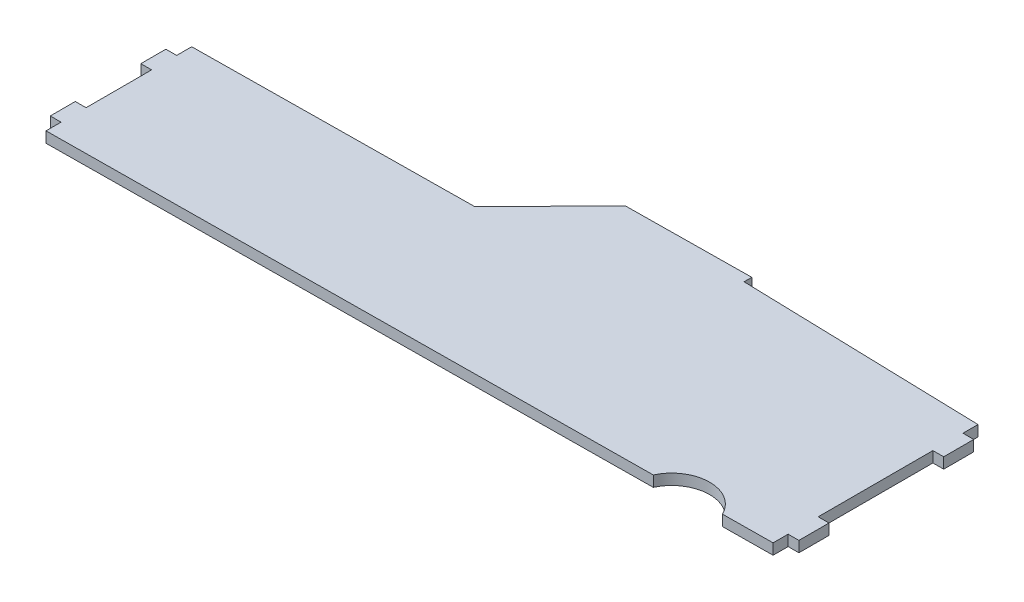
SolidWorks part; units mm, degrees
note: '?' marks a value the reader was unsure of.
material "Acrylic (Medium-high impact)"
ref_plane "Front" through (0, 0, 0) normal (0, 0, 1) x (1, 0, 0)
ref_plane "Top" through (0, 0, 0) normal (0, 1, 0) x (1, 0, 0)
ref_plane "Right" through (0, 0, 0) normal (1, 0, 0) x (0, 0, -1)
ref_axis "side-side" through (80.9, 0, 0) along (-1, 0, 0)?
ref_axis "up-down" through (0, 50, 0) along (0, -1, 0)?
ref_axis "front-back" through (0, 0, -80.9) along (0, 0, 1)?
sketch3d "3DSketch1"
  line L1 (106.3085, 18.7792, 112.386) -> (-144.3396, -7.2886, 112.0046)
  line L2 (106.3085, 18.7792, 112.386) -> (111.2529, -28.6891, 107.3699)
  line L10 (149.9635, -49.7721, 83.9204) -> (150.2559, -52.5791, 110.7725)
  line L11 (146.8969, -20.3316, 84.5177) -> (149.6788, -47.0392, 81.6954)
  line L12 (146.9185, -20.5396, 86.5067) -> (146.8969, -20.3316, 84.5177)
  line L13 (149.752, -47.7417, 83.6322) -> (146.9185, -20.5396, 86.5067)
  line L14 (150.0552, -50.6528, 111.4788) -> (149.752, -47.7417, 83.6322)
  line L15 (147.2218, -23.4506, 114.3533) -> (150.0552, -50.6528, 111.4788)
  line L16 (147.2434, -23.6585, 116.3424) -> (147.2218, -23.4506, 114.3533)
  line L17 (150.0254, -50.3661, 113.5201) -> (147.2434, -23.6585, 116.3424)
  line L18 (149.9635, -49.7721, 83.9204) -> (150.2559, -52.5791, 110.7725)
  line L19 (146.8969, -20.3316, 84.5177) -> (149.6788, -47.0392, 81.6954)
  line L20 (146.9185, -20.5396, 86.5067) -> (146.8969, -20.3316, 84.5177)
  line L21 (149.752, -47.7417, 83.6322) -> (146.9185, -20.5396, 86.5067)
  line L22 (150.0552, -50.6528, 111.4788) -> (149.752, -47.7417, 83.6322)
  line L23 (147.2218, -23.4506, 114.3533) -> (150.0552, -50.6528, 111.4788)
  line L24 (147.2434, -23.6585, 116.3424) -> (147.2218, -23.4506, 114.3533)
  line L25 (150.0254, -50.3661, 113.5201) -> (147.2434, -23.6585, 116.3424)
  arc A2 (149.6788, -47.0392, 81.6954) -> (149.9635, -49.7721, 83.9204) centre (149.7059, -47.2991, 84.1817) ccw
  arc A3 (150.2559, -52.5791, 110.7725) -> (150.0254, -50.3661, 113.5201) centre (149.9983, -50.1062, 111.0338) ccw
  arc A4 (149.6788, -47.0392, 81.6954) -> (149.9635, -49.7721, 83.9204) centre (149.7059, -47.2991, 84.1817) ccw
  arc A5 (150.2559, -52.5791, 110.7725) -> (150.0254, -50.3661, 113.5201) centre (149.9983, -50.1062, 111.0338) ccw
  point P16 (147.2193, -47.5581, 84.1817)
  point P19 (147.5117, -50.3652, 111.0338)
  point P20 (147.2193, -47.5581, 84.1817)
  point P21 (147.5117, -50.3652, 111.0338)
  dimension "D1" = 0
ref_plane "Plane1" through (1.0322, -11.5374, 110.1981) normal (-0.0093, 0.1041, -0.9945) x (-1, -0.001, 0.0093)
sketch "Sketch3" plane through (1.0322, -11.5374, 110.1981) normal (-0.0093, 0.1041, -0.9945) x (-1, -0.001, 0.0093)
  line L0 (-98.6079, 94.7953) -> (-113.8605, -52.442)
  line L1 (-98.6079, 94.7953) -> (205.7196, 63.2694)
  line L2 (-113.8605, -52.442) -> (190.4669, -83.9679)
  line L3 (205.7196, 63.2694) -> (190.4669, -83.9679)
  line L4 (-105.2808, 30.3799) -> (-110.2255, -17.3527) construction
surface "Surface-Plane1" sketch "Sketch3"
sketch "Sketch4" plane through (0, 0, 0) normal (0, 1, 0) x (1, 0, 0)
  line L0 (-199.3464, -113.2829) -> (108.2646, -110.4016)
  line L1 (-126.8098, -112.6035) -> (117.9865, -110.3105) construction
  line L2 (-144.7791, -48.6057) -> (-144.7791, 135.3125)
  line L3 (-144.7791, -48.6057) -> (-144.7791, 135.3125) construction
  line L4 (144.7791, -22.2698) -> (144.7791, 138.5677)
  line L5 (144.7791, -22.2698) -> (144.7791, 164.8582) construction
  line L6 (47.7369, -6.0182) -> (47.7369, 41.5356)
  line L7 (47.7369, -13.6104) -> (47.7369, -10.5185)
  line L8 (47.7369, -6.0182) -> (42.6294, -6.0738)
  line L9 (5.3488, -6.4798) -> (-6.8682, -6.6128)
  line L10 (5.3488, -6.4798) -> (-6.8682, -6.6128) construction
  line L11 (47.7369, -6.0182) -> (42.6294, -6.0738) construction
  line L12 (47.7369, -10.5185) -> (-2.2631, -11.0629)
  line L13 (-143.7791, -100.7619) -> (-143.7791, -94.7619)
  line L14 (143.7791, -98.0684) -> (143.7791, -92.0684)
  line L15 (143.7791, -22.2698) -> (143.7791, -16.2698) construction
  line L16 (144.7791, -22.2698) -> (144.7791, -16.2698) construction
  line L17 (47.7369, -13.6104) -> (143.7791, -16.2698)
  line L18 (5.3978, -10.9795) -> (-6.8192, -11.1126) construction
  line L19 (-143.7791, -42.6057) -> (-31.9347, -41.3878)
  line L20 (-31.9347, -41.3878) -> (-2.2631, -11.0629)
  line L21 (-143.7791, -48.6057) -> (-143.7791, 135.3125) construction
  line L22 (143.7791, -98.0684) -> (123.769, -98.2558)
  line L23 (96.3896, -98.5123) -> (-143.7791, -100.7619)
  line L24 (-143.7791, -94.7619) -> (-148.0791, -94.7619)
  line L25 (-143.7791, -84.7619) -> (-148.0791, -84.7619)
  line L26 (-148.0791, -94.7619) -> (-148.0791, -84.7619)
  line L27 (-143.7791, -84.7619) -> (-143.7791, -58.6057)
  line L28 (-143.7791, -58.6057) -> (-148.0791, -58.6057)
  line L29 (-143.7791, -48.6057) -> (-148.0791, -48.6057)
  line L30 (-148.0791, -58.6057) -> (-148.0791, -48.6057)
  line L31 (-143.7791, -48.6057) -> (-143.7791, -42.6057)
  line L32 (143.7791, -92.0684) -> (148.0791, -92.0684)
  line L33 (143.7791, -22.2698) -> (143.7791, -16.2698)
  line L34 (148.0791, -92.0684) -> (148.0791, -80.0684)
  line L35 (143.7791, -80.0684) -> (148.0791, -80.0684)
  line L36 (-144.7791, -285.6837) -> (-144.7791, -94.7619)
  line L37 (143.7791, -34.2698) -> (148.0791, -34.2698)
  line L38 (143.7791, -22.2698) -> (148.0791, -22.2698)
  line L39 (148.0791, -34.2698) -> (148.0791, -22.2698)
  line L40 (143.7791, -80.0684) -> (143.7791, -34.2698)
  line L41 (-144.7791, -84.7619) -> (-144.7791, -58.6057)
  line L42 (144.7791, -290.0819) -> (144.7791, -92.0684)
  line L43 (-144.7791, -84.7619) -> (-144.7791, -58.6057) construction
  line L44 (-144.7791, -285.6837) -> (-144.7791, -94.7619) construction
  line L45 (144.7791, -80.0684) -> (144.7791, -34.2698)
  line L47 (144.7791, -80.0684) -> (144.7791, -34.2698) construction
  line L48 (144.7791, -290.0819) -> (144.7791, -92.0684) construction
  arc A0 (96.3896, -98.5123) -> (123.769, -98.2558) centre (110.1405, -104.9157) cw
  spline S0 degree 3 poles (104.7126, -12.1869) (117.36, -12.5852) (130.1306, -12.9388) (143.0096, -13.2473) knots 0 0 0 0 1 1 1 1 weights 1 0.999616 0.999616 1
  spline S1 degree 3 poles (104.7126, -12.1869) (117.36, -12.5852) (130.1306, -12.9388) (143.0096, -13.2473) knots 0 0 0 0 1 1 1 1 weights 1 0.999616 0.999616 1 construction
  point P1 (145.9291, -92.0684)
  dimension "D4" = 3
  dimension "D5" = 3
  dimension "D6" = 30
  dimension "D7" = 45
  dimension "D8" = 50
  dimension "D9" = 12
  dimension "D10" = 4.3
  dimension "D11" = 10
  dimension "D12" = 6
  dimension "D13" = 6
  dimension "D14" = 4.3
  dimension "D15" = 12
  dimension "D16" = 6
  dimension "D17" = 6
  dimension "D1" = 4.5
  dimension "D2" = 1
  dimension "D3" = 1
extrude "Boss-Extrude1" add sketch "Sketch4" against normal blind 4.3
